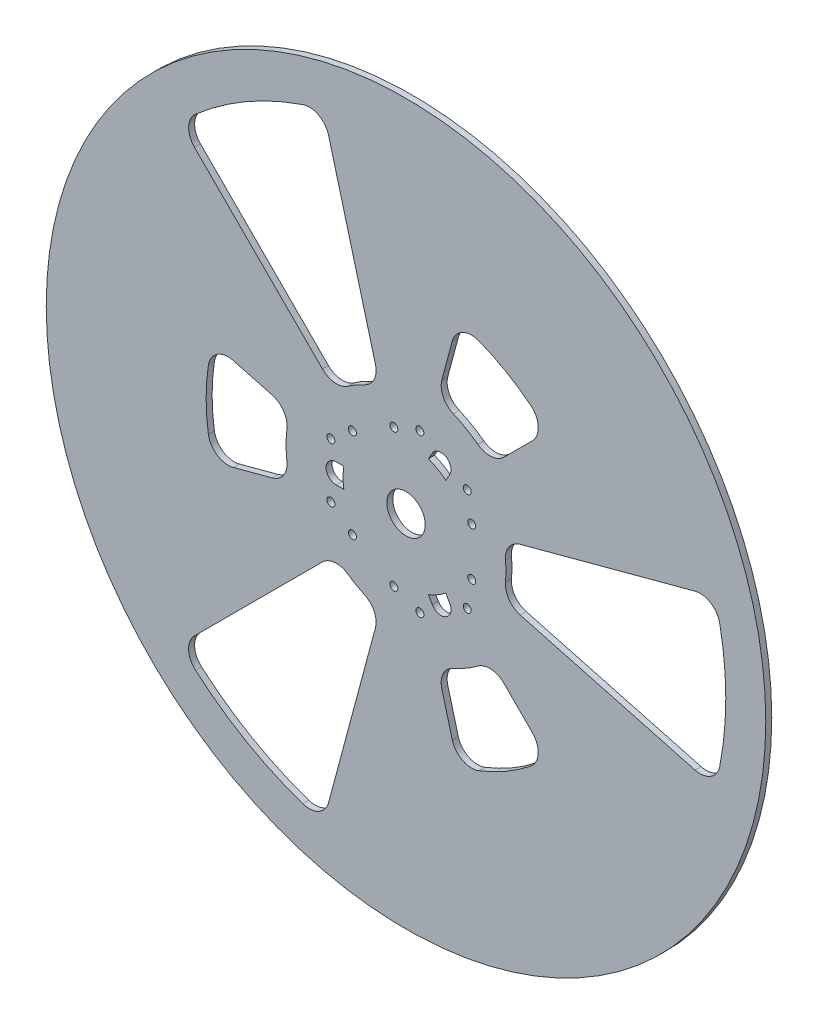
SolidWorks part; units mm, degrees
material "ABS PC"
ref_plane "Front Plane" through (0, 0, 0) normal (0, 0, 1) x (1, 0, 0)
ref_plane "Top Plane" through (0, 0, 0) normal (0, 1, 0) x (1, 0, 0)
ref_plane "Right Plane" through (0, 0, 0) normal (1, 0, 0) x (0, 0, -1)
sketch "Sketch1" plane through (0, 0, 0) normal (0, 0, 1) x (1, 0, 0)
  line L0 (13.1699, 32.8109) -> (11.2202, 29.4339)
  line L1 (-35, -5) -> (-31.1006, -5)
  line L2 (21.8301, 27.8109) -> (19.8804, 24.4339)
  line L3 (13.1699, -32.8109) -> (11.2202, -29.4339)
  line L4 (21.8301, -27.8109) -> (19.8804, -24.4339)
  line L5 (-35, 5) -> (-31.1006, 5)
  line L6 (-15.3119, -57.1449) -> (-38.7365, -144.5665)
  line L7 (57.1449, 15.3119) -> (144.5665, 38.7365)
  line L8 (-66.9213, 17.9315) -> (-86.395, 23.1495)
  line L9 (17.9315, 66.9213) -> (23.1495, 86.395)
  line L10 (17.9315, -66.9213) -> (23.1495, -86.395)
  line L11 (-41.833, 41.833) -> (-105.8301, 105.8301)
  line L12 (-15.3119, 57.1449) -> (-38.7365, 144.5665)
  line L13 (57.1449, -15.3119) -> (144.5665, -38.7365)
  line L14 (48.9898, 48.9898) -> (63.2456, 63.2456)
  line L15 (48.9898, -48.9898) -> (63.2456, -63.2456)
  line L16 (-66.9213, -17.9315) -> (-86.395, -23.1495)
  line L17 (-41.833, -41.833) -> (-105.8301, -105.8301)
  circle A0 centre (0, 0) radius 180
  circle A1 centre (-37.5877, 13.6808) radius 2
  circle A2 centre (-37.5877, -13.6808) radius 2
  circle A3 centre (6.9459, 39.3923) radius 2
  circle A4 centre (6.9459, -39.3923) radius 2
  circle A5 centre (30.6418, -25.7115) radius 2
  circle A6 centre (30.6418, 25.7115) radius 2
  circle A7 centre (0, 0) radius 9.6
  circle A8 centre (-26.8116, 22.4976) radius 2
  circle A9 centre (-6.0777, -34.4683) radius 2
  circle A10 centre (-26.8116, -22.4976) radius 2
  circle A11 centre (-6.0777, 34.4683) radius 2
  circle A12 centre (32.8892, 11.9707) radius 2
  circle A13 centre (32.8892, -11.9707) radius 2
  arc A14 (11.2202, -29.4339) -> (19.8804, -24.4339) centre (0, 0) ccw
  arc A15 (19.8804, 24.4339) -> (11.2202, 29.4339) centre (0, 0) ccw
  arc A16 (-31.1006, 5) -> (-31.1006, -5) centre (0, 0) ccw
  arc A17 (-35, 5) -> (-35, -5) centre (-35, 0) ccw
  arc A18 (13.1699, -32.8109) -> (21.8301, -27.8109) centre (17.5, -30.3109) ccw
  arc A19 (21.8301, 27.8109) -> (13.1699, 32.8109) centre (17.5, 30.3109) ccw
  arc A20 (-59.5796, 7.0905) -> (-66.9213, 17.9315) centre (-69.5095, 8.2723) ccw
  arc A21 (-86.395, 23.1495) -> (-98.8702, 14.9891) centre (-88.9832, 13.4902) ccw
  arc A22 (63.2456, 63.2456) -> (62.4161, 78.1296) centre (56.1745, 70.3166) ccw
  arc A23 (-98.8702, 14.9891) -> (-98.8702, -14.9891) centre (0, 0) ccw
  arc A24 (-105.8301, -105.8301) -> (-105.3429, -120.4279) centre (-98.759, -112.9011) ccw
  arc A25 (156.965, -31.0157) -> (156.965, 31.0157) centre (0, 0) ccw
  arc A26 (-51.6221, 151.4436) -> (-105.3429, 120.4279) centre (0, 0) ccw
  arc A27 (23.6492, -55.1427) -> (17.9315, -66.9213) centre (27.5908, -64.3331) ccw
  arc A28 (57.1449, 15.3119) -> (49.7776, 4.7106) centre (59.7331, 5.6527) ccw
  arc A29 (-105.3429, -120.4279) -> (-51.6221, -151.4436) centre (0, 0) ccw
  arc A30 (36.4542, 93.1187) -> (23.1495, 86.395) centre (32.8087, 83.8068) ccw
  arc A31 (62.4161, 78.1296) -> (36.4542, 93.1187) centre (0, 0) ccw
  arc A32 (17.9315, 66.9213) -> (23.6492, 55.1427) centre (27.5908, 64.3331) ccw
  arc A33 (144.5665, -38.7365) -> (156.965, -31.0157) centre (147.1547, -29.0772) ccw
  arc A34 (62.4161, -78.1296) -> (63.2456, -63.2456) centre (56.1745, -70.3166) ccw
  arc A35 (-51.6221, -151.4436) -> (-38.7365, -144.5665) centre (-48.3957, -141.9783) ccw
  arc A36 (-15.3119, -57.1449) -> (-20.8093, -45.464) centre (-24.9712, -54.5568) ccw
  arc A37 (35.9303, 48.0522) -> (48.9898, 48.9898) centre (41.9187, 56.0609) ccw
  arc A38 (49.7776, -4.7106) -> (49.7776, 4.7106) centre (0, 0) ccw
  arc A39 (23.6492, -55.1427) -> (35.9303, -48.0522) centre (0, 0) ccw
  arc A40 (-28.9683, -40.7534) -> (-20.8093, -45.464) centre (0, 0) ccw
  arc A41 (-98.8702, -14.9891) -> (-86.395, -23.1495) centre (-88.9832, -13.4902) ccw
  arc A42 (-38.7365, 144.5665) -> (-51.6221, 151.4436) centre (-48.3957, 141.9783) ccw
  arc A43 (156.965, 31.0157) -> (144.5665, 38.7365) centre (147.1547, 29.0772) ccw
  arc A44 (35.9303, 48.0522) -> (23.6492, 55.1427) centre (0, 0) ccw
  arc A45 (-59.5796, 7.0905) -> (-59.5796, -7.0905) centre (0, 0) ccw
  arc A46 (49.7776, -4.7106) -> (57.1449, -15.3119) centre (59.7331, -5.6527) ccw
  arc A47 (23.1495, -86.395) -> (36.4542, -93.1187) centre (32.8087, -83.8068) ccw
  arc A48 (-20.8093, 45.464) -> (-15.3119, 57.1449) centre (-24.9712, 54.5568) ccw
  arc A49 (-28.9683, -40.7534) -> (-41.833, -41.833) centre (-34.7619, -48.9041) ccw
  arc A50 (-66.9213, -17.9315) -> (-59.5796, -7.0905) centre (-69.5095, -8.2723) ccw
  arc A51 (48.9898, -48.9898) -> (35.9303, -48.0522) centre (41.9187, -56.0609) ccw
  arc A52 (-20.8093, 45.464) -> (-28.9683, 40.7534) centre (0, 0) ccw
  arc A53 (36.4542, -93.1187) -> (62.4161, -78.1296) centre (0, 0) ccw
  arc A54 (-105.3429, 120.4279) -> (-105.8301, 105.8301) centre (-98.759, 112.9011) ccw
  arc A55 (-41.833, 41.833) -> (-28.9683, 40.7534) centre (-34.7619, 48.9041) ccw
extrude "Boss-Extrude1" add sketch "Sketch1" along normal blind 3
